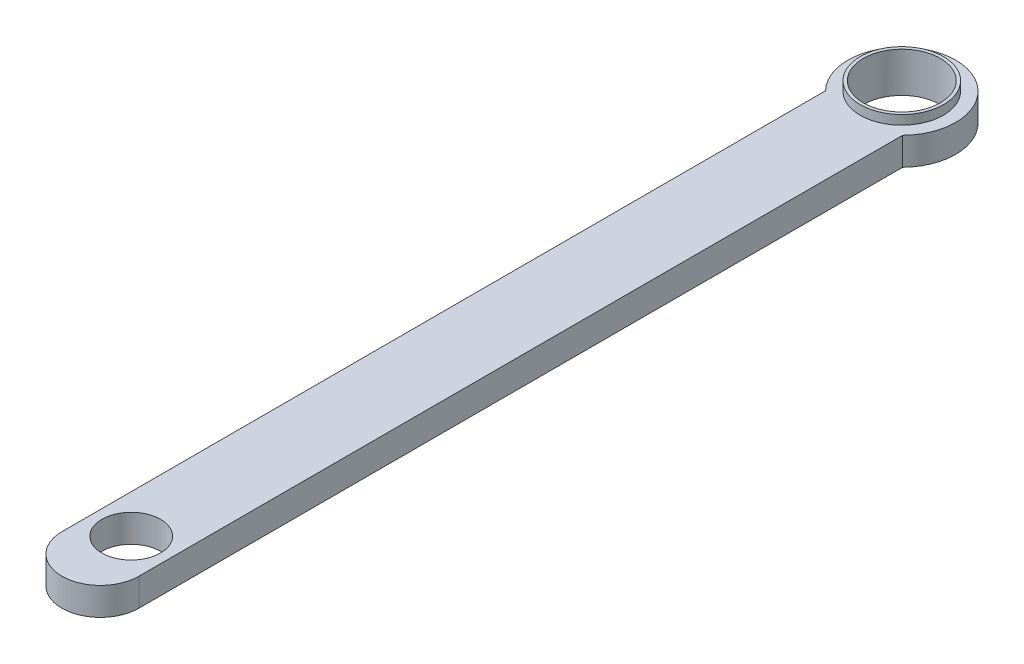
SolidWorks part; units mm, degrees
ref_plane "정면" through (0, 0, 0) normal (0, 0, 1) x (1, 0, 0)
ref_plane "윗면" through (0, 0, 0) normal (0, 1, 0) x (1, 0, 0)
ref_plane "우측면" through (0, 0, 0) normal (1, 0, 0) x (0, 0, -1)
sketch "스케치1" plane through (0, 0, 0) normal (0, 1, 0) x (1, 0, 0)
  line L0 (-12.5, -260) -> (-12.5, -12.2474)
  line L1 (0, 0) -> (0, -260) construction
  line L2 (12.5, -260) -> (12.5, -12.2474)
  arc A1 (12.5, -12.2474) -> (-12.5, -12.2474) centre (0, 0) ccw
  arc A2 (-12.5, -260) -> (12.5, -260) centre (0, -260) ccw
  point P1 (0, 0)
  point P3 (0, 0)
  point P5 (17.4965, 0)
  point P10 (-13.809, -10.75)
  dimension "D2" = 35
  dimension "D3" = 25
  dimension "D4" = 260
extrude "보스-돌출1" add sketch "스케치1" along normal blind 9
sketch "스케치2" plane through (0, 9, 0) normal (0, 1, 0) x (1, 0, 0)
  circle A0 centre (0, 0) radius 12.5
  arc A1 (12.5, -12.2474) -> (-12.5, -12.2474) centre (0, 0) ccw construction
  dimension "D1" = 25
extrude "컷-돌출1" cut sketch "스케치2" against normal through all
sketch "스케치3" plane through (0, 9, 0) normal (0, 1, 0) x (1, 0, 0)
  circle A0 centre (0, 0) radius 13.5
  circle A1 centre (0, 0) radius 12.5 construction
  circle A2 centre (0, 0) radius 12.5
  dimension "D1" = 27
extrude "보스-돌출2" add sketch "스케치3" along normal blind 3
sketch "스케치4" plane through (0, 0, 0) normal (0, -1, 0) x (1, 0, 0)
  circle A0 centre (0, 0) radius 13.5
  circle A1 centre (0, 0) radius 12.5 construction
  circle A2 centre (0, 0) radius 12.5
  dimension "D1" = 27
extrude "보스-돌출3" add sketch "스케치4" along normal blind 1
sketch "스케치5" plane through (0, 9, 0) normal (0, 1, 0) x (1, 0, 0)
  circle A0 centre (0, -250) radius 9.5
  dimension "D1" = 19
  dimension "D2" = 250
extrude "컷-돌출2" cut sketch "스케치5" against normal through all
